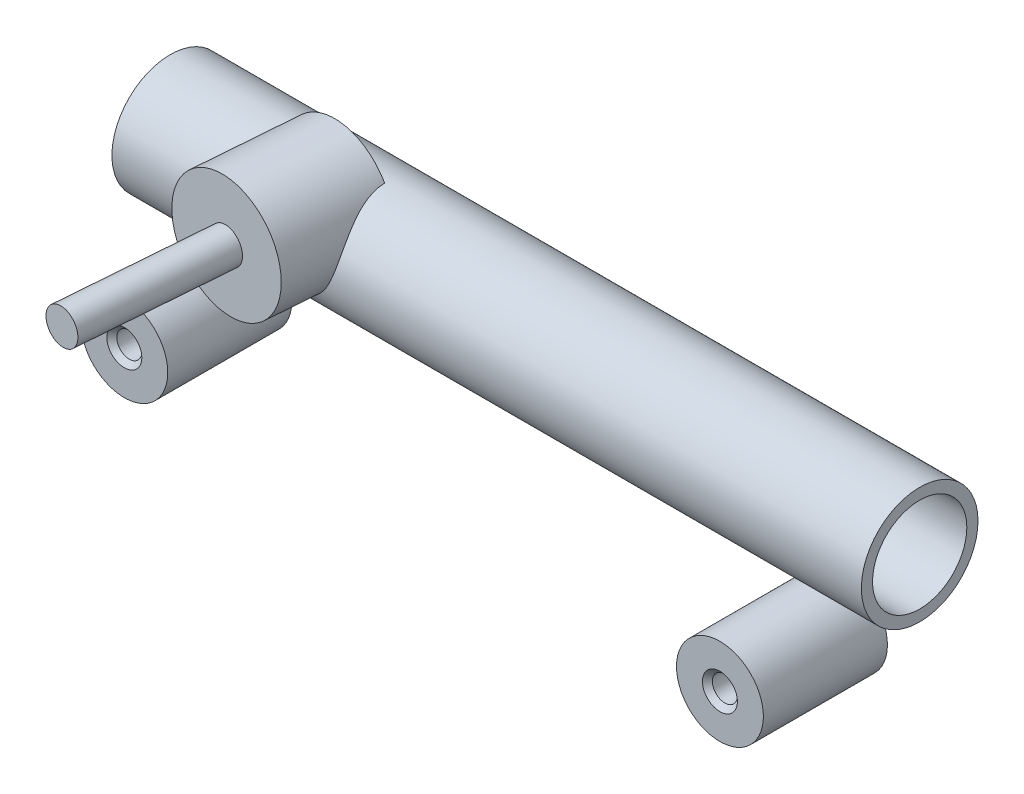
SolidWorks part; units mm, degrees
ref_plane "Płaszczyzna przednia" through (0, 0, 0) normal (0, 0, 1) x (1, 0, 0)
ref_plane "Płaszczyzna górna" through (0, 0, 0) normal (0, 1, 0) x (1, 0, 0)
ref_plane "Płaszczyzna prawa" through (0, 0, 0) normal (1, 0, 0) x (0, 0, -1)
sketch "Szkic1" plane through (0, 0, 0) normal (1, 0, 0) x (0, 0, -1)
  circle A0 centre (0, 0) radius 23.5
  dimension "D1" = 47
extrude "Dodanie-wyciągnięcie1" add sketch "Szkic1" along normal blind 302
ref_plane "Płaszczyzna1" through (0, 23.5, 0) normal (0, 1, 0) x (1, 0, 0)
sketch "Szkic3" plane through (0, 23.5, 0) normal (0, 1, 0) x (1, 0, 0)
  line L0 (0, 0) -> (302, 0) construction
  line L1 (302, -23.5) -> (302, 23.5) construction
sketch "Szkic2" plane through (0, 0, 0) normal (0, 0, 1) x (1, 0, 0)
  line L0 (0, 23.5) -> (0, -23.5) construction
  line L1 (302, 23.5) -> (0, 23.5) construction
  circle A0 centre (31.5, -38) radius 17.5
  dimension "D1" = 35
  dimension "D2" = 31.5
  dimension "D3" = 61.5
extrude "Dodanie-wyciągnięcie2" add sketch "Szkic2" along normal blind 50
sketch "Szkic4" plane through (0, 0, 0) normal (0, 0, -1) x (-1, 0, 0)
  line L0 (-31.5, -38) -> (-323.956, -38) construction
  circle A0 centre (-271.5, -38) radius 17.5
  circle A1 centre (-31.5, -38) radius 17.5 construction
  dimension "D1" = 240
  dimension "D2" = 35
extrude "Dodanie-wyciągnięcie3" add sketch "Szkic4" against normal blind 50
sketch "Szkic5" plane through (0, 0, 50) normal (0, 0, 1) x (1, 0, 0)
  circle A0 centre (31.5, -38) radius 5.05
  circle A1 centre (271.5, -38) radius 5.05
  dimension "D1" = 10.1
  dimension "D2" = 10.1
extrude "Wytnij-wyciągnięcie1" cut sketch "Szkic5" against normal blind 50
chamfer "Sfazowanie1" distance 2 angle 45 4 edges at (36.55, -38, 0) (276.55, -38, 0) (276.55, -38, 50) (36.55, -38, 50)
sketch "Szkic7" plane through (0, 23.5, 0) normal (0, 1, 0) x (1, 0, 0)
  line L0 (68, 0) -> (64.6945, -42) construction
  line L1 (0, 0) -> (302, 0) construction
  line L2 (0, 23.5) -> (0, -23.5) construction
  line L3 (68, 0) -> (68, -42) construction
  dimension "D1" = 68
  dimension "D2" = 4.5
  dimension "D3" = 42
ref_plane "Płaszczyzna2" through (0, -55.5, 0) normal (0, -1, 0) x (-1, 0, 0)
ref_plane "Płaszczyzna3" through (64.6945, 23.5, 42) normal (-0.0785, 0, 0.9969) x (0.9969, 0, 0.0785)
sketch "Szkic8" plane through (64.6945, 23.5, 42) normal (-0.0785, 0, 0.9969) x (0.9969, 0, 0.0785)
  line L0 (0, 0) -> (0, -79) construction
  line L1 (-95.2904, -79) -> (-40.2904, -79) construction
  circle A0 centre (0, -13.25) radius 24
  dimension "D2" = 48
  dimension "D1" = 65.75
extrude "Dodanie-wyciągnięcie4" add sketch "Szkic8" against normal up to vertex (42.1299 mm away) up to point (68, 23.5, 0)
sketch "Szkic10" plane through (0, 0, 0) normal (-1, 0, 0) x (0, 0, 1)
  line L0 (23.5, 0) -> (103.5, 0) construction
  circle A0 centre (0, 0) radius 23.5 construction
  dimension "D1" = 80
sketch "Szkic11" plane through (0, 23.5, 0) normal (0, 1, 0) x (1, 0, 0)
  line L0 (64.6945, -42) -> (59.8544, -103.5) construction
  line L1 (68, 0) -> (64.6945, -42) construction
  dimension "D1" = 61.6902
sketch "Szkic12" plane through (-2.8869, 0, 36.6812) normal (-0.0785, 0, 0.9969) x (0.9969, 0, 0.0785)
  circle A0 centre (67.7904, 10.25) radius 7
  dimension "D1" = 14
extrude "Dodanie-wyciągnięcie5" add sketch "Szkic12" along normal up to vertex (61.6902 mm away) up to point (59.8544, 23.5, 103.5)
sketch "Szkic6" plane through (0, 0, 0) normal (-1, 0, 0) x (0, 0, 1)
  circle A0 centre (0, 0) radius 19
  dimension "D1" = 38
extrude "Wytnij-wyciągnięcie2" cut sketch "Szkic6" against normal up to surface (302 mm away) up to face at (302, 0, -23.5)
sketch "Szkic13" plane through (64.6945, 23.5, 42) normal (-0.0785, 0, 0.9969) x (0.9969, 0, 0.0785)
  circle A0 centre (0, -13.25) radius 7
extrude "Dodanie-wyciągnięcie6" add sketch "Szkic13" against normal blind 50
sketch "Szkic14" plane through (0, 0, 0) normal (0, 0, 1) x (1, 0, 0)
  line L0 (151, 23.5) -> (151, -7.2498) construction
  line L1 (0, 23.5) -> (302, 23.5) construction
